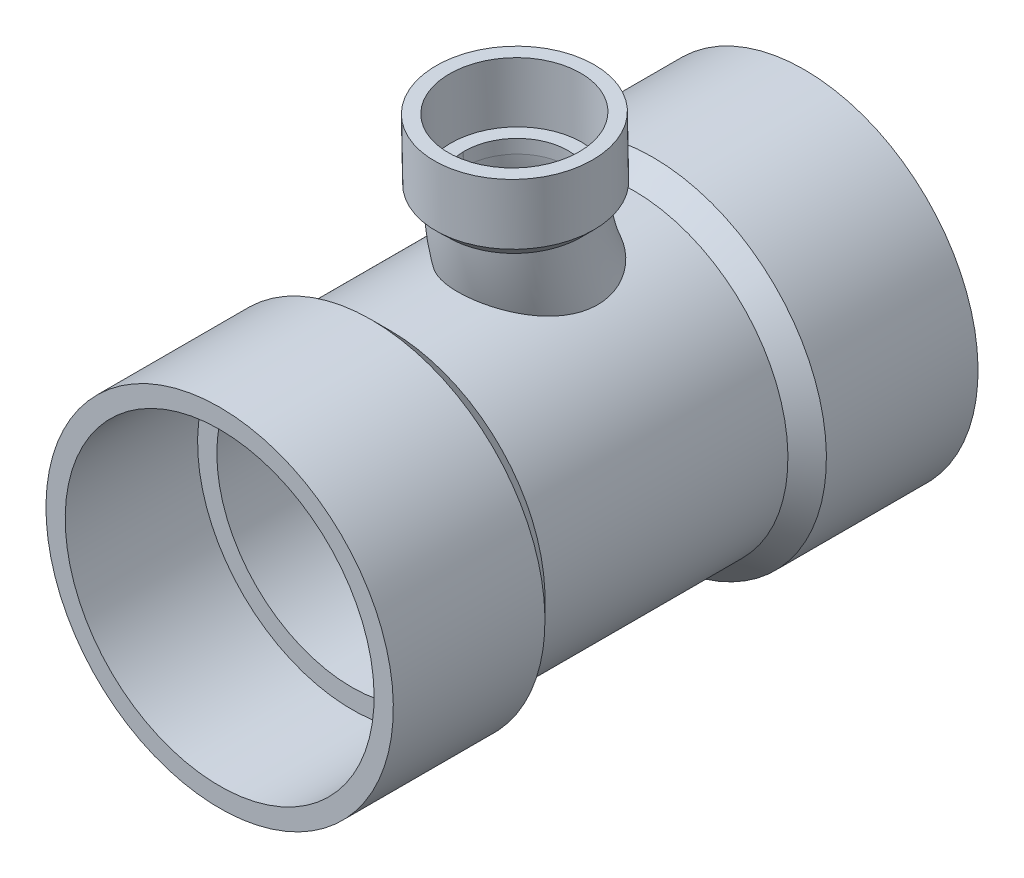
SolidWorks part; units mm, degrees
ref_plane "Front Plane" through (0, 0, 0) normal (0, 0, 1) x (1, 0, 0)
ref_plane "Top Plane" through (0, 0, 0) normal (0, 1, 0) x (1, 0, 0)
ref_plane "Right Plane" through (0, 0, 0) normal (1, 0, 0) x (0, 0, -1)
sketch "RunRoute" plane through (0, 0, 0) normal (0, 0, 1) x (1, 0, 0)
  circle A0 centre (0, 0) radius 44.45
  circle A1 centre (0, 0) radius 38.9128
sketch "Sketch2" plane through (0, 0, 0) normal (1, 0, 0) x (0, 0, -1)
  line L0 (0, 0) -> (-1.3301, 63.5) construction
  line L1 (0, 0) -> (-48.4187, 0) construction
  line L2 (0, 0) -> (43.6562, 0) construction
  arc A0 (-1.3301, 63.5) -> (43.6562, 0) centre (68.0302, 64.9529) ccw
  point P8 (0, 0)
  dimension "DimensionC" = 43.6562
  dimension "DimensionB" = 92.075
  dimension "Angle" = 88.8
  dimension "DimensionA" = 63.5
ref_plane "Outlet Plane" through (0, 63.5, 1.3301) normal (0, 0.9998, 0.0209) x (1, 0, 0)
sketch "OutletRoute" plane through (0, 63.5, 1.3301) normal (0, 0.9998, 0.0209) x (1, 0, 0)
  circle A0 centre (0, 0) radius 19.05
  circle A1 centre (0, 0) radius 15.0876
extrude "Boss-Extrude1" add sketch "RunRoute" along normal up to vertex (48.4188 mm away) and the other way up to vertex (43.6562 mm away) up to point (0, 0, 48.4187) other way up to point (0, 0, -43.6562)
sketch "Sketch6" plane through (0, 0, 0) normal (1, 0, 0) x (0, 0, -1)
  line L0 (17.7157, 63.899) -> (-20.376, 63.101) construction
  line L1 (43.6562, 44.45) -> (-48.4187, 44.45) construction
  line L2 (17.7157, 63.899) -> (17.0887, 93.8332) construction
  line L3 (-20.376, 63.101) -> (-20.9875, 92.2953) construction
  line L4 (43.6562, 44.45) -> (-48.4187, 44.45) construction
  line L6 (13.7542, 63.816) -> (-16.4144, 63.184) construction
  arc A0 (17.7157, 63.899) -> (22.0705, 44.45) centre (68.0302, 64.9529) ccw
  arc A1 (-20.376, 63.101) -> (-17.9856, 44.45) centre (68.0302, 64.9529) ccw
  arc A2 (-16.4144, 63.184) -> (-13.9067, 44.45) centre (68.0302, 64.9529) ccw
  arc A3 (13.7542, 63.816) -> (17.7628, 44.45) centre (68.0302, 64.9529) ccw
  arc A4 (-1.3301, 63.5) -> (43.6562, 0) centre (68.0302, 64.9529) ccw construction
ref_plane "Plane2" through (0, 44.45, 0) normal (0, -1, 0) x (-1, 0, 0)
sweep "Sweep1" add profiles "OutletRoute" path "Sketch2"
sketch "Sketch3" plane through (0, 0, 0) normal (1, 0, 0) x (0, 0, -1)
  line L0 (43.6562, 0) -> (43.6562, -38.9128) construction
  line L1 (43.6562, -44.45) -> (81.7563, -44.45)
  line L2 (81.7563, -44.45) -> (81.7563, -49.9872)
  line L3 (81.7563, -49.9872) -> (38.1191, -49.9872)
  line L4 (38.1191, -49.9872) -> (32.5818, -44.45)
  line L5 (32.5818, -44.45) -> (32.5818, -38.9128)
  line L6 (32.5818, -38.9128) -> (43.6562, -38.9128)
  line L7 (43.6562, -38.9128) -> (43.6562, -44.45)
  line L8 (0, 0) -> (43.6562, 0) construction
  line L11 (43.6562, 0) -> (81.7562, 0) construction
  line L12 (81.7562, 0) -> (81.7563, -44.45) construction
  line L13 (-48.4187, -44.45) -> (43.6562, -44.45) construction
  line L14 (-48.4187, 0) -> (-86.5187, 0) construction
  line L15 (-86.5187, 0) -> (-86.5187, -44.45) construction
  line L16 (-86.5187, -44.45) -> (-86.5187, -49.9872)
  line L17 (-86.5187, -49.9872) -> (-42.8815, -49.9872)
  line L18 (-42.8815, -49.9872) -> (-37.3443, -44.45)
  line L19 (-37.3443, -44.45) -> (-37.3443, -38.9128)
  line L20 (-37.3443, -38.9128) -> (-48.4187, -38.9128)
  line L21 (-48.4187, -38.9128) -> (-48.4187, -44.45)
  line L22 (-48.4187, -44.45) -> (-86.5187, -44.45)
  line L25 (17.3502, 81.3449) -> (21.3118, 81.4279)
  line L26 (-1.3301, 63.5) -> (-1.6956, 80.946) construction
  line L27 (0, 0) -> (-1.3301, 63.5) construction
  line L28 (-1.6956, 80.946) -> (17.3502, 81.3449) construction
  line L29 (21.3118, 81.4279) -> (21.6805, 63.8257)
  line L30 (17.3502, 81.3449) -> (17.7157, 63.899)
  line L31 (21.6805, 63.8257) -> (17.9549, 59.9407)
  line L32 (17.9549, 59.9407) -> (13.8371, 59.8544)
  line L33 (13.8371, 59.8544) -> (13.7542, 63.816)
  line L34 (13.7542, 63.816) -> (17.7157, 63.899)
  arc A0 (17.7157, 63.899) -> (22.0705, 44.45) centre (68.0302, 64.9529) ccw construction
  dimension "D3" = 45
  dimension "D5" = 45
  dimension "D7" = 45
  dimension "OutletHubD" = 3.9624
  dimension "D9" = 3.9624
extrude "Cut-Extrude1" cut sketch "RunRoute<2>" against normal through all both and the other way through all contours A1 region at (0, 0, 0)
sketch "RunRoute<2>" plane through (0, 0, 0) normal (0, 0, 1) x (1, 0, 0) same geometry as "RunRoute"
revolve "Revolve1" add sketch "Sketch3" angle 360 about L26 region at (0, 69.9322, -18.8487)
revolve "Revolve2" add sketch "Sketch3<5>" angle 360 about L14 region at (0, -46.1073, -54.5942) region at (0, -46.1073, 59.3567)
sketch "Sketch3<5>" plane through (0, 0, 0) normal (1, 0, 0) x (0, 0, -1) same geometry as "Sketch3"
ref_plane "Plane3" through (0, 0, 48.4187) normal (0, 0, 1) x (1, 0, 0)
ref_plane "Plane4" through (0, 0, -43.6562) normal (0, 0, -1) x (-1, 0, 0)
other "CPoint1" parameters "Diameter"=76.2, "StubLength"=19.05
ref_axis "Axis1" through (0, 0, 58.4187) along (0, 0, -1)
other "CPoint2" parameters "Diameter"=76.2, "StubLength"=0
ref_axis "Axis2" through (0, 0, -53.6562) along (0, 0, 1)
other "CPoint3" parameters "Diameter"=38.1, "StubLength"=152.4
ref_axis "Axis3" through (0, 73.4978, 1.5396) along (0, -0.9998, -0.0209)
other "RPoint1"
equation "\"D1@Sketch3\"=\"HubD@RunRoute\""
equation "\"D4@Sketch3\"=\"D1@Sketch3\""
equation "\"D6@Sketch3\"=\"D4@Sketch3\""
equation "\"D9@Sketch3\"=\"OutletHubD@Sketch3\""
equation "\"D8@Sketch3\"=\"OutletRoute@OutletRoute\""
equation "\"D2@Sketch3\"=\"Diameter@RunRoute\""
